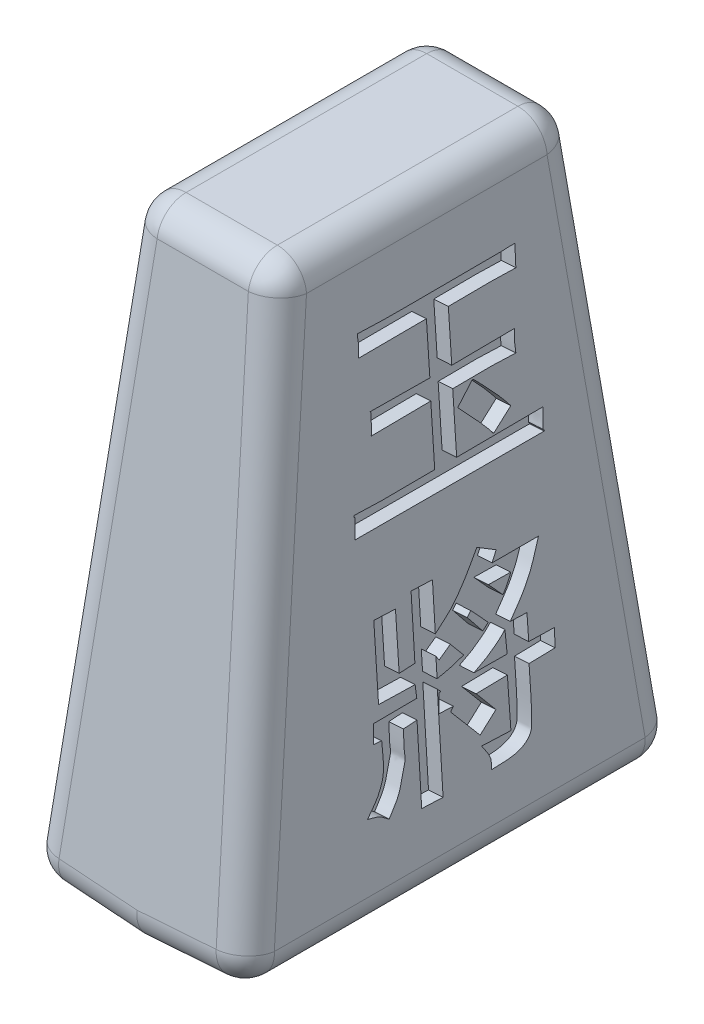
SolidWorks part; units mm, degrees
ref_plane "Płaszczyzna przednia" through (0, 0, 0) normal (0, 0, 1) x (1, 0, 0)
ref_plane "Płaszczyzna górna" through (0, 0, 0) normal (0, 1, 0) x (1, 0, 0)
ref_plane "Płaszczyzna prawa" through (0, 0, 0) normal (1, 0, 0) x (0, 0, -1)
sketch "Szkic1" plane through (0, 0, 0) normal (0, 0, 1) x (1, 0, 0)
  line L0 (0, 0) -> (0, 40)
  line L1 (3.1225, 40) -> (-3.1225, 40)
  line L2 (-5.1185, 38.1262) -> (-7.3738, 2.4704)
  line L3 (-5.504, 0.3481) -> (0, 0)
  line L4 (5.504, 0.3481) -> (0, 0)
  line L5 (5.1185, 38.1262) -> (7.3738, 2.4704)
  arc A0 (-3.1225, 40) -> (-5.1185, 38.1262) centre (-3.1225, 38) ccw
  arc A1 (-7.3738, 2.4704) -> (-5.504, 0.3481) centre (-5.3777, 2.3441) ccw
  arc A2 (7.3738, 2.4704) -> (5.504, 0.3481) centre (5.3777, 2.3441) cw
  arc A3 (3.1225, 40) -> (5.1185, 38.1262) centre (3.1225, 38) cw
  point P7 (-5, 40)
  point P10 (-7.5, 0.4744)
  point P17 (7.5, 0.4744)
  point P18 (5, 40)
  dimension "D5" = 2
  dimension "D1" = 40
  dimension "D2" = 90
  dimension "D3" = 5
  dimension "D4" = 7.5
extrude "Dodanie-wyciągnięcie1" add sketch "Szkic1" along normal blind 30 contours L2 A1 L3 L0 L1 A0 | A3 L1 L0 L4 A2 L5 region at (-3.1441, 18.7866, 0) region at (3.1441, 18.7866, 0)
ref_plane "Płaszczyzna1" through (5.1225, 0, 0) normal (1, 0, 0) x (0, 0, -1)
ref_plane "Płaszczyzna2" through (15.1225, 0, 0) normal (1, 0, 0) x (0, 0, -1)
sketch "Szkic7" plane through (15.1225, 0, 0) normal (1, 0, 0) x (0, 0, -1)
  line L0 (-25, 40) -> (-5, 40)
  line L1 (-30, 40) -> (0, 40) construction
  line L2 (-5, 40) -> (0, 0)
  line L3 (0, 0) -> (-30, 0)
  line L4 (-30, 0) -> (0, 0) construction
  line L5 (-15, 0) -> (-15, 40)
  line L6 (-25, 40) -> (-30, 0)
  line L8 (0, 0) -> (-30, 0)
  line L9 (0, 0) -> (0, 40)
  line L10 (0, 40) -> (-30, 40)
  line L11 (-30, 0) -> (-30, 40)
  dimension "D1" = 10
  dimension "D2" = 15
  dimension "D3" = 40
extrude "Wytnij-wyciągnięcie11" cut sketch "Szkic7" against normal through all and the other way through all contours L11 L6 L10 | L9 L10 L2 region at (15.1225, 26.6667, 28.3333) region at (15.1225, 26.6667, 1.6667)
fillet "Zaokrąglenie2" radius 2 18 edges at (0, 40, 5) (-4.4914, 39.4582, 4.9323) (-6.2461, 20.2983, 2.5373) (-6.8784, 1.022, 0.1278) (-2.752, 0.1741, 0.0218) (2.752, 0.1741, 0.0218) (6.8784, 1.022, 0.1278) (6.2461, 20.2983, 2.5373) (4.4914, 39.4582, 4.9323) (4.4914, 39.4582, 25.0677) (6.2461, 20.2983, 27.4627) (6.8784, 1.022, 29.8722) (2.752, 0.1741, 29.9782) (-2.752, 0.1741, 29.9782) (-6.8784, 1.022, 29.8722) (-6.2461, 20.2983, 27.4627) (-4.4914, 39.4582, 25.0677) (0, 40, 25)
sketch "Szkic10" plane through (7.5, 0.4744, 0) normal (0.998, 0.0631, 0) x (0, 0, -1)
  line L0 (341.3333, 1024) -> (1706.6667, 1024) construction
  line L1 (-9.2168, 33.8142) -> (-9.2368, 32.4142)
  line L2 (-13.8568, 32.4342) -> (-13.8368, 29.0342)
  line L3 (-13.8368, 29.0342) -> (-9.5368, 29.0742)
  line L4 (-13.8568, 27.6942) -> (-13.8368, 23.7342)
  line L5 (-13.8368, 23.7342) -> (-7.9168, 23.7742)
  line L6 (-7.9168, 22.4142) -> (-7.9368, 22.3742)
  line L7 (-7.9368, 22.3742) -> (-20.8768, 22.3942)
  line L8 (-20.8768, 23.7142) -> (-20.8568, 23.7942)
  line L9 (-15.3368, 23.7542) -> (-15.3568, 27.7142)
  line L10 (-15.3568, 27.7142) -> (-19.4368, 27.6742)
  line L11 (-19.4368, 29.0742) -> (-15.3368, 29.0342)
  line L12 (-15.3368, 29.0342) -> (-15.3568, 32.4542)
  line L13 (-15.3568, 32.4542) -> (-19.9968, 32.4342)
  line L14 (-10.0568, 24.8742) -> (-11.2768, 23.8942)
  line L15 (-12.8168, 18.0542) -> (-11.5368, 17.2942)
  line L16 (-11.5368, 17.2942) -> (-11.8568, 16.6942)
  line L17 (-11.8568, 16.6942) -> (-8.6768, 16.6942)
  line L18 (-10.8568, 12.8342) -> (-9.7168, 12.7942)
  line L19 (-9.7168, 12.7942) -> (-9.6968, 11.1142)
  line L20 (-9.6968, 11.1142) -> (-7.9368, 11.0742)
  line L21 (-7.9368, 11.0742) -> (-7.9768, 9.9142)
  line L22 (-7.9768, 9.9142) -> (-9.7568, 9.8742)
  line L23 (-13.1968, 6.7942) -> (-11.1968, 6.7142)
  line L24 (-11.1968, 6.7142) -> (-11.2368, 9.9342)
  line L25 (-11.2368, 9.9342) -> (-13.3768, 9.8942)
  line L26 (-13.3768, 9.8942) -> (-12.1168, 8.3742)
  line L27 (-12.1168, 8.3742) -> (-13.2568, 7.4542)
  line L28 (-13.2568, 7.4542) -> (-15.1368, 9.6942)
  line L29 (-15.1368, 9.6942) -> (-14.9368, 9.9342)
  line L30 (-14.9368, 9.9342) -> (-15.9168, 9.9742)
  line L31 (-15.9168, 9.9742) -> (-15.8568, 11.1342)
  line L32 (-15.8568, 11.1342) -> (-15.7168, 11.1742)
  line L33 (-15.7168, 11.1742) -> (-15.9368, 11.3942)
  line L34 (-15.9368, 11.3942) -> (-15.9368, 5.1742)
  line L35 (-15.9368, 5.1742) -> (-17.3968, 5.2342)
  line L36 (-17.3968, 5.2342) -> (-17.3968, 10.3342)
  line L37 (-17.3968, 10.3342) -> (-18.3368, 10.2742)
  line L38 (-19.8168, 10.3142) -> (-20.3768, 10.3542)
  line L39 (-20.3768, 10.3542) -> (-20.3168, 11.5342)
  line L40 (-20.3168, 11.5342) -> (-17.3368, 11.5542)
  line L41 (-17.3368, 11.5542) -> (-17.3968, 12.3742)
  line L42 (-17.3968, 12.3742) -> (-19.8968, 12.4342)
  line L43 (-19.8968, 12.4342) -> (-19.9168, 17.2942)
  line L44 (-19.9168, 17.2942) -> (-18.4368, 17.2342)
  line L45 (-18.4368, 17.2342) -> (-18.4168, 13.5142)
  line L46 (-18.4168, 13.5142) -> (-17.3368, 13.5742)
  line L47 (-17.3368, 13.5742) -> (-17.3368, 17.7342)
  line L48 (-17.3368, 17.7342) -> (-15.8768, 17.6742)
  line L49 (-15.8768, 17.6742) -> (-15.8768, 14.5542)
  line L50 (-12.1768, 15.5942) -> (-10.6568, 15.5742)
  line L51 (-11.2568, 14.5742) -> (-12.1768, 15.5942)
  line L52 (-13.4368, 14.7142) -> (-12.3168, 13.4942)
  line L53 (-12.3168, 13.4942) -> (-12.7168, 13.1942)
  line L54 (-12.7168, 13.1942) -> (-13.6968, 14.4342)
  line L55 (-13.6968, 14.4342) -> (-13.4368, 14.7142)
  line L56 (-14.9168, 13.4942) -> (-14.0768, 12.4742)
  line L57 (-15.9168, 11.9942) -> (-15.9168, 13.2942)
  line L58 (-15.9168, 13.2942) -> (-15.7168, 12.9742)
  line L59 (-15.7168, 12.9742) -> (-14.9168, 13.4942)
  line L60 (-11.2368, 12.5542) -> (-11.1768, 11.1142)
  line L61 (-11.1768, 11.1142) -> (-13.4368, 11.1342)
  spline S0 degree 3 poles (-19.9968, 33.8342) (-19.2901, 33.8142) (-18.5837, 33.777) (-17.8768, 33.7742) (-15.2102, 33.7636) (-12.5434, 33.7809) (-9.8768, 33.7942) (-9.8674, 33.7942) (-9.8662, 33.8139) (-9.8568, 33.8142) (-9.6436, 33.8206) (-9.4301, 33.8142) (-9.2168, 33.8142) knots 0 0 0 0 1 1 1 2 2 2 3 3 3 4 4 4 4
  spline S1 degree 3 poles (-9.2368, 32.4142) (-9.8101, 32.4275) (-10.3833, 32.4517) (-10.9568, 32.4542) (-11.9235, 32.4584) (-12.8901, 32.4408) (-13.8568, 32.4342) knots 0 0 0 0 1 1 1 2 2 2 2
  spline S2 degree 3 poles (-9.5368, 29.0742) (-9.5501, 28.7942) (-9.5768, 28.5145) (-9.5768, 28.2342) (-9.5768, 28.0404) (-9.5501, 27.8475) (-9.5368, 27.6542) knots 0 0 0 0 1 1 1 2 2 2 2
  spline S3 degree 3 poles (-9.5368, 27.6542) (-10.1367, 27.6782) (-10.7365, 27.7142) (-11.3368, 27.7142) (-12.1768, 27.7142) (-13.0168, 27.7008) (-13.8568, 27.6942) knots 0 0 0 0 1 1 1 2 2 2 2
  spline S4 degree 3 poles (-7.9168, 23.7742) (-7.9301, 23.5808) (-7.9539, 23.3879) (-7.9568, 23.1942) (-7.9678, 22.456) (-8.1148, 22.6122) (-7.9168, 22.4142) knots 0 0 0 0 1 1 1 2 2 2 2
  spline S5 degree 3 poles (-20.8768, 22.3942) (-20.8635, 22.5875) (-20.8398, 22.7804) (-20.8368, 22.9742) (-20.8261, 23.6726) (-20.6883, 23.5256) (-20.8768, 23.7142) knots 0 0 0 0 1 1 1 2 2 2 2
  spline S6 degree 3 poles (-20.8568, 23.7942) (-20.2301, 23.7742) (-19.6038, 23.7387) (-18.9768, 23.7342) (-17.7635, 23.7254) (-16.5501, 23.7475) (-15.3368, 23.7542) knots 0 0 0 0 1 1 1 2 2 2 2
  spline S7 degree 3 poles (-19.4368, 27.6742) (-19.3961, 27.9183) (-19.3845, 28.1668) (-19.3768, 28.4142) (-19.3765, 28.4236) (-19.3962, 28.4248) (-19.3968, 28.4342) (-19.4374, 29.0839) (-19.2697, 28.907) (-19.4368, 29.0742) knots 0 0 0 0 1 1 1 2 2 2 3 3 3 3
  spline S8 degree 3 poles (-19.9968, 32.4342) (-19.9835, 32.7342) (-19.9633, 33.0339) (-19.9568, 33.3342) (-19.9566, 33.3436) (-19.9761, 33.3448) (-19.9768, 33.3542) (-19.9896, 33.5138) (-19.9901, 33.6742) (-19.9968, 33.8342) knots 0 0 0 0 1 1 1 2 2 2 3 3 3 3
  spline S9 degree 3 poles (-12.5168, 27.5742) (-12.4968, 27.5675) (-12.4727, 27.568) (-12.4568, 27.5542) (-12.3499, 27.4615) (-12.2551, 27.3558) (-12.1568, 27.2542) (-11.424, 26.4961) (-10.6908, 25.7195) (-10.0568, 24.8742) knots 0 0 0 0 1 1 1 2 2 2 3 3 3 3
  spline S10 degree 3 poles (-11.2768, 23.8942) (-11.2968, 23.9008) (-11.3219, 23.8993) (-11.3368, 23.9142) (-11.3708, 23.9482) (-11.3889, 23.995) (-11.4168, 24.0342) (-11.5554, 24.2282) (-11.7226, 24.4119) (-11.8768, 24.5942) (-12.4202, 25.2364) (-12.9941, 25.8472) (-13.5768, 26.4542) knots 0 0 0 0 1 1 1 2 2 2 3 3 3 4 4 4 4
  spline S11 degree 3 poles (-13.5768, 26.4542) (-13.5701, 26.4742) (-13.5704, 26.4981) (-13.5568, 26.5142) (-13.4959, 26.5861) (-13.4228, 26.6469) (-13.3568, 26.7142) (-13.0762, 27.0002) (-12.7968, 27.2875) (-12.5168, 27.5742) knots 0 0 0 0 1 1 1 2 2 2 3 3 3 3
  spline S12 degree 3 poles (-8.6768, 16.6942) (-8.9301, 16.0742) (-9.1259, 15.4274) (-9.4368, 14.8342) (-9.8163, 14.11) (-10.3403, 13.468) (-10.8568, 12.8342) knots 0 0 0 0 1 1 1 2 2 2 2
  spline S13 degree 3 poles (-9.7568, 9.8742) (-9.7768, 8.6608) (-9.6816, 7.4401) (-9.8168, 6.2342) (-9.8452, 5.9806) (-10.0342, 5.7493) (-10.2368, 5.5942) (-10.4816, 5.4068) (-10.7937, 5.3102) (-11.0968, 5.2542) (-11.5961, 5.1619) (-12.1101, 5.1875) (-12.6168, 5.1542) knots 0 0 0 0 1 1 1 2 2 2 3 3 3 4 4 4 4
  spline S14 degree 3 poles (-12.6168, 5.1542) (-12.6301, 5.3942) (-12.5767, 5.6476) (-12.6568, 5.8742) (-12.7754, 6.2094) (-13.0168, 6.4875) (-13.1968, 6.7942) knots 0 0 0 0 1 1 1 2 2 2 2
  spline S15 degree 3 poles (-18.3368, 10.2742) (-18.4176, 8.1531) (-18.1953, 8.8387) (-18.4368, 8.1142) (-18.5901, 7.6542) (-18.6872, 7.1714) (-18.8968, 6.7342) (-19.0774, 6.3573) (-19.3635, 6.0408) (-19.5968, 5.6942) knots 0 0 0 0 1 1 1 2 2 2 3 3 3 3
  spline S16 degree 3 poles (-19.5968, 5.6942) (-19.8101, 5.8408) (-20.0027, 6.0236) (-20.2368, 6.1342) (-20.4886, 6.2531) (-20.7701, 6.2942) (-21.0368, 6.3742) knots 0 0 0 0 1 1 1 2 2 2 2
  spline S17 degree 3 poles (-21.0368, 6.3742) (-20.7701, 6.7075) (-20.4512, 7.0051) (-20.2368, 7.3742) (-20.0396, 7.7135) (-19.8723, 8.0856) (-19.8168, 8.4742) (-19.7301, 9.0813) (-19.8168, 9.7008) (-19.8168, 10.3142) knots 0 0 0 0 1 1 1 2 2 2 3 3 3 3
  spline S18 degree 3 poles (-15.8768, 14.5542) (-15.4235, 14.9342) (-14.9146, 15.2563) (-14.5168, 15.6942) (-13.8649, 16.4118) (-13.3373, 17.2362) (-12.8168, 18.0542) knots 0 0 0 0 1 1 1 2 2 2 2
  spline S19 degree 3 poles (-10.6568, 15.5742) (-10.7021, 15.4157) (-10.772, 15.3026) (-10.8568, 15.1542) (-10.9047, 15.0704) (-10.9424, 14.9919) (-10.9968, 14.9142) (-11.0396, 14.8531) (-11.18, 14.6126) (-11.2568, 14.5742) knots 0 0 0 0 1 1 1 2 2 2 3 3 3 3
  spline S20 degree 3 poles (-14.0768, 12.4742) (-14.0835, 12.4675) (-14.0879, 12.4572) (-14.0968, 12.4542) (-14.2822, 12.3903) (-14.4689, 12.3301) (-14.6568, 12.2742) (-14.8676, 12.2114) (-15.0814, 12.1585) (-15.2968, 12.1142) (-15.5006, 12.0722) (-15.7137, 12.045) (-15.9168, 11.9942) knots 0 0 0 0 1 1 1 2 2 2 3 3 3 4 4 4 4
  spline S21 degree 3 poles (-13.4368, 11.1342) (-13.4301, 11.1408) (-13.4253, 11.1501) (-13.4168, 11.1542) (-13.1403, 11.2851) (-12.9052, 11.3921) (-12.6368, 11.5342) (-12.5494, 11.5805) (-12.4618, 11.6431) (-12.3768, 11.6942) (-11.9702, 11.9381) (-11.5742, 12.2168) (-11.2368, 12.5542) knots 0 0 0 0 1 1 1 2 2 2 3 3 3 4 4 4 4
extrude "Wytnij-wyciągnięcie15" cut sketch "Szkic10" against normal blind 1 contours S8 L13 L12 L11 S7 L10 L9 S6 L8 S5 L7 L6 S4 L5 L4 S3 S2 L3 L2 S1 L1 S0 | S11 S10 L14 S9 | S18 L49 L48 L47 L46 L45 L44 L43 L42 L41 L40 L39 L38 S17 S16 S15 L37 L36 L35 L34 L33 L32 L31 L30 L29 L28 L27 L26 L25 L24 L23 S14 S13 L22 L21 L20 L19 L18 S12 L17 L16 L15 L54 L55 L52 L53 L50 S19 L51 region at (5.74, 28.3005, 14.532) region at (5.8764, 26.1446, 11.7708) region at (6.767, 12.0631, 14.5821)
